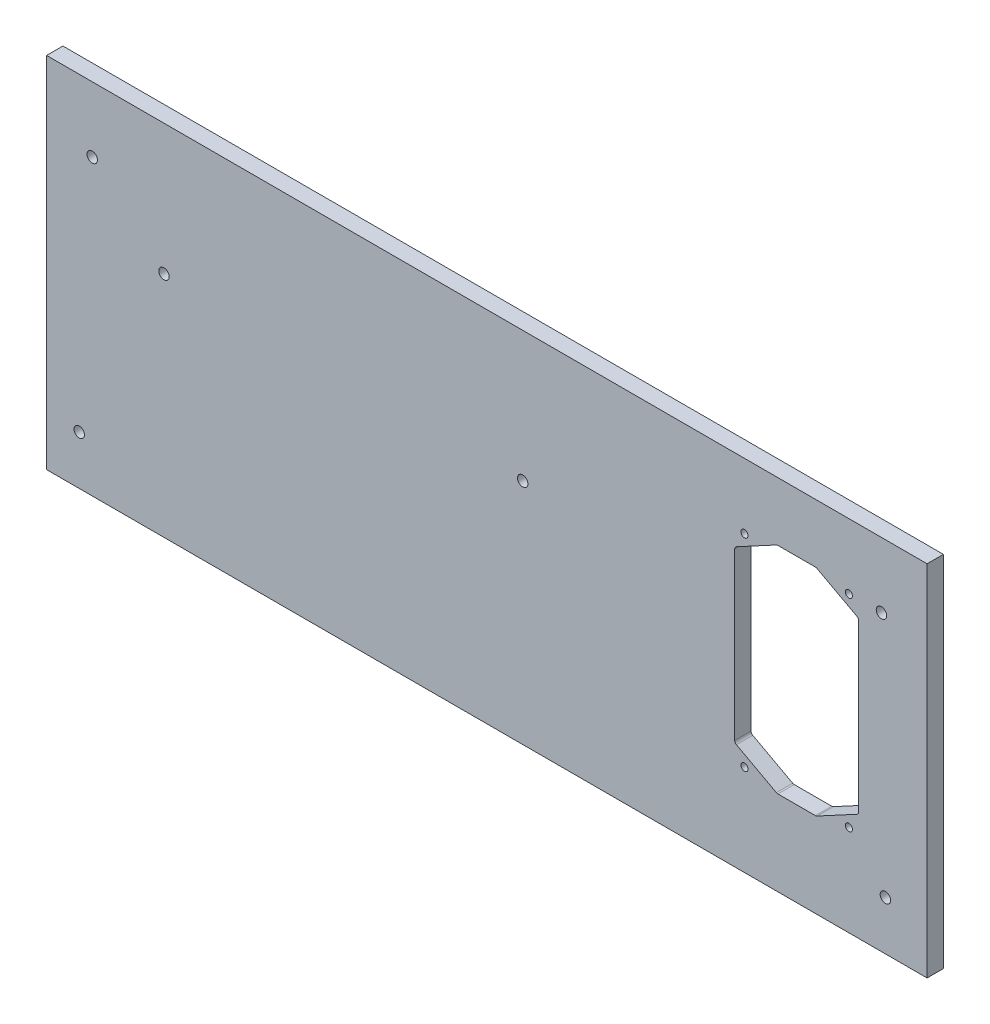
SolidWorks part; units mm, degrees
material "Acrylic (Medium-high impact)"
ref_plane "Front Plane" through (0, 0, 0) normal (0, 0, 1) x (1, 0, 0)
ref_plane "Top Plane" through (0, 0, 0) normal (0, 1, 0) x (1, 0, 0)
ref_plane "Right Plane" through (0, 0, 0) normal (1, 0, 0) x (0, 0, -1)
sketch "Sketch1" plane through (0, 0, 0) normal (0, 0, 1) x (1, 0, 0)
  line L1 (135, -55) -> (-135, -55)
  line L2 (135, -55) -> (135, 55)
  line L3 (135, 55) -> (-135, 55)
  line L4 (-135, -55) -> (-135, 55)
  line L5 (135, -55) -> (-135, 55) construction
  line L6 (135, 55) -> (-135, -55) construction
  point P0 (0, 0)
  dimension "D1" = 110
  dimension "D2" = 270
extrude "Base" add sketch "Sketch1" along normal mid plane 5
sketch "Sketch4" plane through (0, 0, -2.5) normal (0, 0, -1) x (-1, 0, 0)
  line L0 (-101, 37) -> (-114, 30)
  line L1 (-89, -29) -> (-101, -29)
  line L2 (-76, -22) -> (-76, 30)
  line L3 (-89, 37) -> (-101, 37)
  line L4 (-114, -22) -> (-114, 30)
  line L5 (-76, -29) -> (-114, 37) construction
  line L6 (-76, 37) -> (-114, -29) construction
  line L7 (-79, -27) -> (-111, -27) construction
  line L8 (-79, -27) -> (-79, 35) construction
  line L9 (-79, 35) -> (-111, 35) construction
  line L10 (-111, -27) -> (-111, 35) construction
  line L11 (-79, -27) -> (-111, 35) construction
  line L12 (-79, 35) -> (-111, -27) construction
  line L13 (-101, -29) -> (-114, -22)
  line L14 (-95, 4) -> (-95, 17.8562) construction
  line L15 (-76, 30) -> (-89, 37)
  line L16 (-76, -22) -> (-89, -29)
  line L17 (-135, -55) -> (-135, 55) construction
  line L18 (135, -55) -> (-135, -55) construction
  circle A0 centre (-79, 35) radius 1.1
  circle A1 centre (-111, 35) radius 1.1
  circle A2 centre (-111, -27) radius 1.1
  circle A3 centre (-79, -27) radius 1.1
  point P0 (-95, 4)
  point P14 (-95, 4)
  dimension "D1" = 2.2
  dimension "D2" = 62
  dimension "D3" = 32
  dimension "D4" = 38
  dimension "D5" = 66
  dimension "D6" = 13
  dimension "D7" = 7
  dimension "D8" = 13
  dimension "D9" = 7
  dimension "D10" = 7
  dimension "D11" = 13
  dimension "D12" = 13
  dimension "D13" = 7
  dimension "D14" = 40
  dimension "D15" = 59
extrude "Cut-Extrude1" cut sketch "Sketch4" against normal through all
fillet "Fillet1" radius 1 8 edges at (76, 30, 0) (89, -29, 0) (101, -29, 0) (114, -22, 0) (114, 30, 0) (101, 37, 0) (89, 37, 0) (76, -22, 0)
hole_wizard "Ø3.2 (3.2) MountHoles" positions "Sketch5" profile "Sketch6" hole size "Ø3.2" standard "ANSI Metric" end condition through all
sketch "Sketch5" plane through (0, 0, -2.5) normal (0, 0, -1) x (-1, 0, 0)
  line L0 (135, -55) -> (-135, -55) construction
  line L1 (135, 55) -> (135, -55) construction
  line L2 (-135, 55) -> (135, 55) construction
  line L3 (-135, -55) -> (-135, 55) construction
  point P0 (-121, 35)
  point P2 (-122.2168, -40)
  point P4 (125, -40)
  point P6 (121, 35)
  point P11 (0, 0)
  point P12 (0, 0)
  point P13 (0, 0)
  point P14 (0, 0)
  dimension "D1" = 15
  dimension "D2" = 10
  dimension "D3" = 20
  dimension "D4" = 14
  dimension "D5" = 14
sketch "Sketch6" plane through (121, 35, -2.5) normal (1, 0, 0) x (0, 1, 0)
  line L0 (0, 0) -> (0, 5)
  line L1 (0, 5) -> (1.6, 5)
  line L2 (1.6, 5) -> (1.6, 1.65)
  line L3 (1.6, 1.65) -> (3.25, 0)
  line L5 (3.25, 0) -> (0, 0)
  line L6 (-1.6, 1.65) -> (-3.25, 0) construction
  line L11 (0, -6.35) -> (0, 107.95) construction
  dimension "Thru Hole Dia." = 3.2
  dimension "Thru Hole Depth" = 5
  dimension "Near C'Sink Dia." = 6.5
  dimension "Near C'Sink Angle" = 90
hole_wizard "Ø3.2 (3.2) MiddlePartHoles" positions "Sketch7" profile "Sketch8" hole size "Ø3.2" standard "ANSI Metric" end condition through all
sketch "Sketch7" plane through (0, 0, -2.5) normal (0, 0, -1) x (-1, 0, 0)
  line L0 (135, 55) -> (135, -55) construction
  line L1 (-135, 55) -> (135, 55) construction
  point P0 (-11, 15)
  point P2 (99, 15)
  point P9 (0, 0)
  dimension "D1" = 36
  dimension "D2" = 110
  dimension "D3" = 40
sketch "Sketch8" plane through (11, 15, -2.5) normal (1, 0, 0) x (0, 1, 0)
  line L0 (0, 0) -> (0, 5)
  line L1 (0, 5) -> (1.6, 5)
  line L2 (1.6, 5) -> (1.6, 1.65)
  line L3 (1.6, 1.65) -> (3.25, 0)
  line L5 (3.25, 0) -> (0, 0)
  line L6 (-1.6, 1.65) -> (-3.25, 0) construction
  line L11 (0, -6.35) -> (0, 107.95) construction
  dimension "Thru Hole Dia." = 3.2
  dimension "Thru Hole Depth" = 5
  dimension "Near C'Sink Dia." = 6.5
  dimension "Near C'Sink Angle" = 90
equation "\"D5@Sketch5\"=\"D4@Sketch5\""
